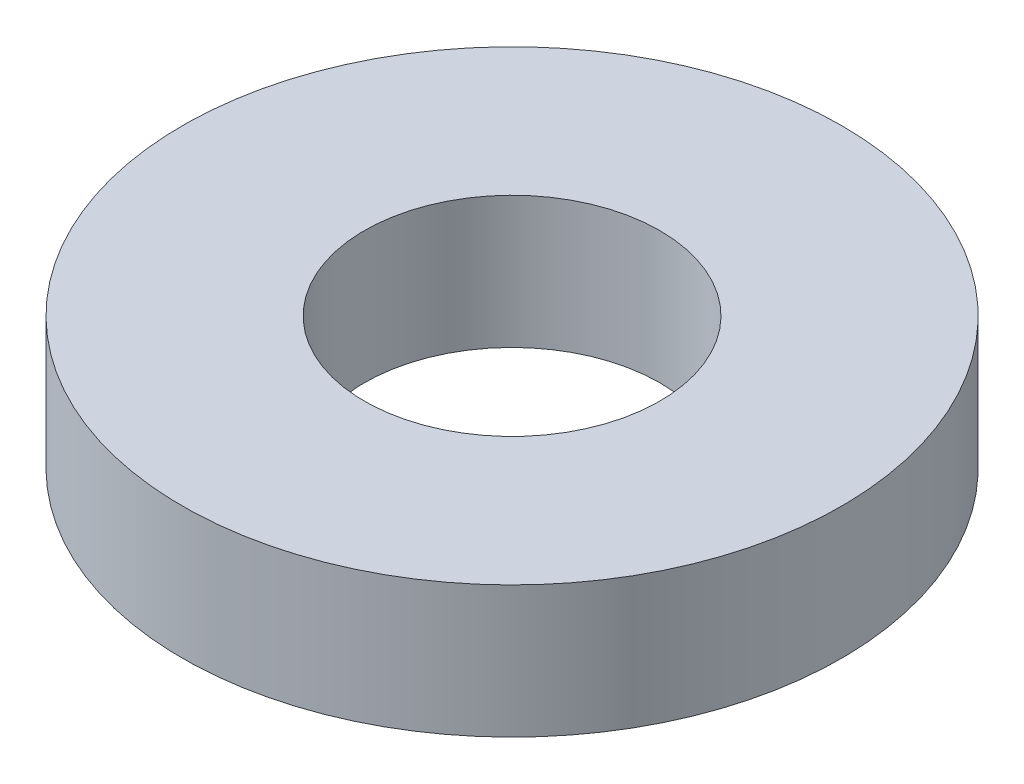
SolidWorks part; units mm, degrees
ref_plane "Front Plane" through (0, 0, 0) normal (0, 0, 1) x (1, 0, 0)
ref_plane "Top Plane" through (0, 0, 0) normal (0, 1, 0) x (1, 0, 0)
ref_plane "Right Plane" through (0, 0, 0) normal (1, 0, 0) x (0, 0, -1)
sketch "Sketch1" plane through (0, 0, 0) normal (0, 1, 0) x (1, 0, 0)
  circle A0 centre (0, 0) radius 72.5
  dimension "FLANGE_OD" = 145
extrude "Boss-Extrude1" add sketch "Sketch1" along normal blind 29
sketch "Sketch2" plane through (0, 0, 0) normal (0, 1, 0) x (1, 0, 0)
  circle A0 centre (0, 0) radius 32.5
  dimension "BORE_D" = 65
extrude "Cut-Extrude1" cut sketch "Sketch2" along normal through all
sketch "Sketch3" plane through (0, 29, 0) normal (0, 1, 0) x (1, 0, 0)
  circle A0 centre (0, 0) radius 27.0664 construction
  circle A1 centre (-27.0664, 0) radius 2.7572
  dimension "BOLT_D" = 5.5144
  dimension "BOLT_PCD" = 54.1328
extrude "Cut-Extrude2" cut sketch "Sketch3" against normal blind 23.5578 rebuild error yes
pattern_circular "CirPattern1" count 4 over 360 rebuild error yes
